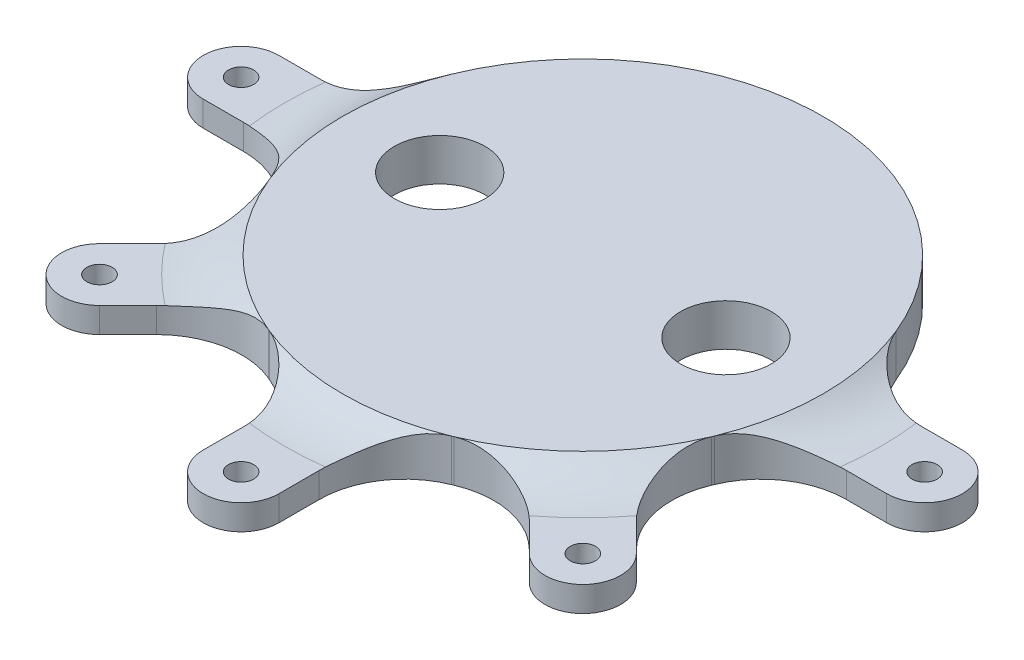
SolidWorks part; units mm, degrees
ref_plane "Front Plane" through (0, 0, 0) normal (0, 0, 1) x (1, 0, 0)
ref_plane "Top Plane" through (0, 0, 0) normal (0, 1, 0) x (1, 0, 0)
ref_plane "Right Plane" through (0, 0, 0) normal (1, 0, 0) x (0, 0, -1)
sketch "Sketch1" plane through (0, 0, 0) normal (0, 1, 0) x (1, 0, 0)
  line L0 (0, 28.575) -> (0, -28.575) construction
  circle A0 centre (0, 0) radius 28.575
  circle A1 centre (-17.018, 0) radius 5.3975
  circle A2 centre (17.018, 0) radius 5.3975
  dimension "D1" = 57.15
  dimension "D3" = 10.795
  dimension "D2" = 34.036
extrude "Boss-Extrude1" add sketch "Sketch1" along normal blind 5 contours L0 A0 A1 | A0 L0 A2 region at (19.7538, 0, -19.7538) region at (-0.639, 0, 0)
sketch "Sketch2" plane through (0, 0, 0) normal (0, 1, 0) x (1, 0, 0)
  line L0 (0, 28.575) -> (0, -28.575) construction
  line L3 (4.5, -40.64) -> (4.5, -28.2184)
  line L4 (-4.5, -40.64) -> (-4.5, -28.2184)
  line L9 (-25.5548, -31.9188) -> (-16.7715, -23.1354)
  line L10 (-31.9188, -25.5548) -> (-23.1354, -16.7715)
  line L11 (-40.64, -4.5) -> (-28.2184, -4.5)
  line L12 (-40.64, 4.5) -> (-28.2184, 4.5)
  line L13 (31.9188, -25.5548) -> (23.1354, -16.7715)
  line L14 (25.5548, -31.9188) -> (16.7715, -23.1354)
  line L15 (40.64, 4.5) -> (28.2184, 4.5)
  line L16 (40.64, -4.5) -> (28.2184, -4.5)
  circle A7 centre (0, 0) radius 28.575 construction
  circle A14 centre (0, 0) radius 40.64 construction
  circle A15 centre (0, -40.64) radius 1.5
  arc A16 (-4.5, -40.64) -> (4.5, -40.64) centre (0, -40.64) ccw
  arc A18 (-4.5, -28.2184) -> (4.5, -28.2184) centre (0, 0) ccw
  arc A20 (-4.5, -28.2184) -> (4.5, -28.2184) centre (0, 0) ccw
  circle A25 centre (-28.7368, -28.7368) radius 1.5
  arc A26 (-31.9188, -25.5548) -> (-25.5548, -31.9188) centre (-28.7368, -28.7368) ccw
  arc A27 (-23.1354, -16.7715) -> (-16.7715, -23.1354) centre (0, 0) ccw
  arc A28 (-23.1354, -16.7715) -> (-16.7715, -23.1354) centre (0, 0) ccw
  circle A29 centre (-40.64, 0) radius 1.5
  arc A30 (-40.64, 4.5) -> (-40.64, -4.5) centre (-40.64, 0) ccw
  arc A31 (-28.2184, 4.5) -> (-28.2184, -4.5) centre (0, 0) ccw
  arc A32 (-28.2184, 4.5) -> (-28.2184, -4.5) centre (0, 0) ccw
  circle A33 centre (28.7368, -28.7368) radius 1.5
  arc A34 (25.5548, -31.9188) -> (31.9188, -25.5548) centre (28.7368, -28.7368) ccw
  arc A35 (16.7715, -23.1354) -> (23.1354, -16.7715) centre (0, 0) ccw
  arc A36 (16.7715, -23.1354) -> (23.1354, -16.7715) centre (0, 0) ccw
  circle A37 centre (40.64, 0) radius 1.5
  arc A38 (40.64, -4.5) -> (40.64, 4.5) centre (40.64, 0) ccw
  arc A39 (28.2184, -4.5) -> (28.2184, 4.5) centre (0, 0) ccw
  arc A40 (28.2184, -4.5) -> (28.2184, 4.5) centre (0, 0) ccw
  point P12 (0, 0)
  point P26 (0, 0)
  point P40 (0, 0)
  dimension "D1" = 4.5
  dimension "D2" = 3
  dimension "D3" = 81.28
  dimension "D4" = 3
extrude "Boss-Extrude2" add sketch "Sketch2" along normal blind 3 contours A18 L4 A16 L3 A15 | A25 | A31 L12 A30 L11 A29 | A35 L14 A34 L13 A33 | A39 L16 A38 L15 A37 region at (0, 0, 36.1213) region at (-25.5416, 0, 25.5416) region at (-36.1213, 0, 0) region at (25.5416, 0, 25.5416) region at (36.1213, 0, 0)
fillet "Fillet1" radius 12.7 5 edges at (0, 3, 28.575) (-20.2056, 3, 20.2056) (28.575, 3, 0) (20.2056, 3, 20.2056) (-28.575, 3, 0)
fillet "Fillet2" radius 10.16 10 edges at (4.5, 2.5, 28.2184) (-4.5, 2.5, 28.2184) (28.2184, 2.5, -4.5) (28.2184, 2.5, 4.5) (23.1354, 2.5, 16.7715) (-28.2184, 2.5, -4.5) (-28.2184, 2.5, 4.5) (16.7715, 2.5, 23.1354) (-23.1354, 2.5, 16.7715) (-16.7715, 2.5, 23.1354)
sketch "Sketch4" plane through (0, 0, 0) normal (0, 1, 0) x (1, 0, 0)
  circle A0 centre (0, 0) radius 37.465
  circle A1 centre (0, 0) radius 40.64
  dimension "D1" = 74.93
